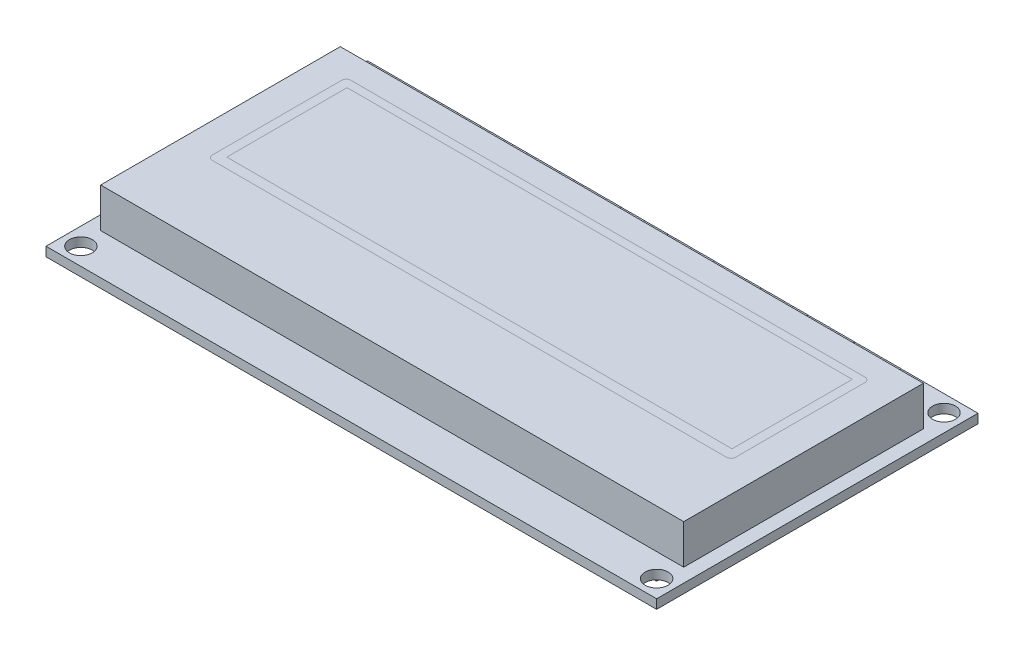
SolidWorks part; units mm, degrees
ref_plane "Front Plane" through (0, 0, 0) normal (0, 0, 1) x (1, 0, 0)
ref_plane "Top Plane" through (0, 0, 0) normal (0, 1, 0) x (1, 0, 0)
ref_plane "Right Plane" through (0, 0, 0) normal (1, 0, 0) x (0, 0, -1)
sketch "Sketch2" plane through (0, 0, 0) normal (0, 1, 0) x (1, 0, 0)
  line L1 (33.25, -17.5) -> (-33.25, -17.5)
  line L2 (33.25, -17.5) -> (33.25, 17.5)
  line L3 (33.25, 17.5) -> (-33.25, 17.5)
  line L4 (-33.25, -17.5) -> (-33.25, 17.5)
  line L5 (33.25, -17.5) -> (-33.25, 17.5) construction
  line L6 (33.25, 17.5) -> (-33.25, -17.5) construction
  point P0 (0, 0)
  dimension "D1" = 66.5
  dimension "D2" = 35
extrude "Boss-Extrude1" add sketch "Sketch2" along normal mid plane 1
hole_wizard "Ø2.5 (2.5) Diameter Hole1" positions "Sketch5" profile "Sketch3" hole size "Ø2.5" standard "ANSI Metric" end condition through all
sketch "Sketch5" plane through (0, 0.5, 0) normal (0, 1, 0) x (1, 0, 0)
  line L0 (-33.25, -17.5) -> (33.25, -17.5) construction
  line L1 (-33.25, 17.5) -> (-33.25, -17.5) construction
  point P0 (-31.35, -15.6)
  point P2 (-31.35, 15.7)
  point P4 (31.35, 15.7)
  point P6 (31.35, -15.6)
  dimension "D1" = 1.9
  dimension "D2" = 62.7
  dimension "D3" = 1.9
  dimension "D4" = 31.3
sketch "Sketch3" plane through (-31.35, 0.5, 15.6) normal (1, 0, 0) x (0, 0, 1)
  line L0 (0, 0) -> (0, 1)
  line L1 (0, 1) -> (1.25, 1)
  line L2 (1.25, 1) -> (1.25, 0)
  line L5 (1.25, 0) -> (0, 0)
  line L11 (0, -6.35) -> (0, 107.95) construction
  dimension "Thru Hole Dia." = 2.5
  dimension "Thru Hole Depth" = 1
hole_wizard "Ø0.8 (0.8) Diameter Hole1" positions "Sketch7" profile "Sketch6" hole size "Ø0.8" standard "ANSI Metric" end condition through all
sketch "Sketch7" plane through (0, 0.5, 0) normal (0, 1, 0) x (1, 0, 0)
  line L0 (-24.16, 14.9) -> (-21.62, 14.9) construction
  line L1 (-33.25, 17.5) -> (-33.25, -17.5) construction
  line L4 (33.25, 17.5) -> (-33.25, 17.5) construction
  point P0 (-24.16, 14.9)
  point P6 (-21.62, 14.9)
  point P7 (-19.08, 14.9)
  point P8 (-16.54, 14.9)
  point P9 (-14, 14.9)
  point P10 (-11.46, 14.9)
  point P11 (-8.92, 14.9)
  point P12 (-6.38, 14.9)
  point P13 (-3.84, 14.9)
  point P14 (-1.3, 14.9)
  point P15 (1.24, 14.9)
  point P16 (3.78, 14.9)
  point P17 (6.32, 14.9)
  point P18 (8.86, 14.9)
  point P19 (11.4, 14.9)
  point P20 (13.94, 14.9)
  point P21 (16.48, 14.9)
  point P22 (19.02, 14.9)
  point P23 (21.56, 14.9)
  point P24 (24.1, 14.9)
  dimension "D5" = 2.6
  dimension "D2" = 2.54
  dimension "D3" = 48.26
  dimension "D4" = 9.09
  dimension "D1" = 20
sketch "Sketch6" plane through (-24.16, 0.5, -14.9) normal (1, 0, 0) x (0, 0, 1)
  line L0 (0, 0) -> (0, 1)
  line L1 (0, 1) -> (0.4, 1)
  line L2 (0.4, 1) -> (0.4, 0)
  line L5 (0.4, 0) -> (0, 0)
  line L11 (0, -6.35) -> (0, 107.95) construction
  dimension "Thru Hole Dia." = 0.8
  dimension "Thru Hole Depth" = 1
sketch "Sketch8" plane through (0, 0.5, 0) normal (0, 1, 0) x (1, 0, 0)
  line L0 (-24.96, 14.9) -> (-24.96, 17.5)
  line L1 (33.25, 17.5) -> (-33.25, 17.5) construction
  line L2 (-24.96, 17.5) -> (-23.36, 17.5)
  line L3 (-23.36, 17.5) -> (-23.36, 14.9)
  arc A0 (-24.96, 14.9) -> (-23.36, 14.9) centre (-24.16, 14.9) ccw
  circle A2 centre (-24.16, 14.9) radius 0.4 construction
  circle A3 centre (-24.16, 14.9) radius 0.4
  dimension "D1" = 1.6
  dimension "D2" = 3.4
extrude "Boss-Extrude2" add sketch "Sketch8" along normal blind 0.01
pattern_linear "LPattern1" count 20 spacing 2.54 along (1, 0, 0) of "Boss-Extrude2"
mirror "Mirror3" about plane through (0, 0, 0) normal (0, 1, 0) of "Boss-Extrude2", "LPattern1"
sketch "Sketch10" plane through (0, 0.5, 0) normal (0, 1, 0) x (1, 0, 0)
  line L0 (-33.25, 17.5) -> (-33.25, -17.5) construction
  line L1 (31.75, -13.05) -> (-31.75, -13.05)
  line L2 (31.75, -13.05) -> (31.75, 13.05)
  line L3 (31.75, 13.05) -> (-31.75, 13.05)
  line L4 (-31.75, -13.05) -> (-31.75, 13.05)
  line L5 (31.75, -13.05) -> (-31.75, 13.05) construction
  line L6 (31.75, 13.05) -> (-31.75, -13.05) construction
  line L7 (-33.25, -17.5) -> (33.25, -17.5) construction
  point P0 (0, 0)
  dimension "D1" = 63.5
  dimension "D2" = 26.1
  dimension "D3" = 1.5
  dimension "D4" = 4.45
extrude "Boss-Extrude3" add sketch "Sketch10" along normal blind 4.3
sketch "Sketch11" plane through (0, 4.8, 0) normal (0, 1, 0) x (1, 0, 0)
  line L0 (-33.25, 17.5) -> (-33.25, -17.5) construction
  line L1 (28, -4.65) -> (-28, -4.65)
  line L2 (28.5, -4.15) -> (28.5, 9.95)
  line L3 (28, 10.45) -> (-28, 10.45)
  line L4 (-28.5, -4.15) -> (-28.5, 9.95)
  line L5 (28.5, -4.65) -> (-28.5, 10.45) construction
  line L6 (28.5, 10.45) -> (-28.5, -4.65) construction
  line L7 (-33.25, -17.5) -> (33.25, -17.5) construction
  arc A0 (-28, -4.65) -> (-28.5, -4.15) centre (-28, -4.15) cw
  arc A1 (28, -4.65) -> (28.5, -4.15) centre (28, -4.15) ccw
  arc A2 (28.5, 9.95) -> (28, 10.45) centre (28, 9.95) ccw
  arc A3 (-28, 10.45) -> (-28.5, 9.95) centre (-28, 9.95) ccw
  point P0 (0, 2.9)
  dimension "D5" = 0.5
  dimension "D1" = 15.1
  dimension "D2" = 57
  dimension "D3" = 4.75
  dimension "D4" = 12.85
split line "Split Line1"
sketch "Sketch12" plane through (0, 4.8, 0) normal (0, 1, 0) x (1, 0, 0)
  line L0 (-33.25, -17.5) -> (33.25, -17.5) construction
  line L1 (27.51, -3.55) -> (-27.51, -3.55)
  line L2 (27.51, -3.55) -> (27.51, 9.55)
  line L3 (27.51, 9.55) -> (-27.51, 9.55)
  line L4 (-27.51, -3.55) -> (-27.51, 9.55)
  line L5 (27.51, -3.55) -> (-27.51, 9.55) construction
  line L6 (27.51, 9.55) -> (-27.51, -3.55) construction
  line L7 (-33.25, 17.5) -> (-33.25, -17.5) construction
  point P0 (0, 3)
  dimension "D1" = 55.02
  dimension "D2" = 13.1
  dimension "D3" = 13.95
  dimension "D4" = 5.74
split line "Split Line2"
sketch "Sketch13" plane through (0, -0.5, 0) normal (0, -1, 0) x (1, 0, 0)
  line L1 (-28.1, 12.35) -> (28.1, 12.35)
  line L2 (-28.1, 12.35) -> (-28.1, -12.1)
  line L3 (-28.1, -12.1) -> (28.1, -12.1)
  line L4 (28.1, 12.35) -> (28.1, -12.1)
  line L5 (-28.1, 12.35) -> (28.1, -12.1) construction
  line L6 (-28.1, -12.1) -> (28.1, 12.35) construction
  arc A2 (24.9, -14.9) -> (23.3, -14.9) centre (24.1, -14.9) ccw construction
  circle A11 centre (31.35, 15.6) radius 1.25 construction
  circle A13 centre (-31.35, 15.6) radius 1.25 construction
  point P0 (0, 0.125)
  dimension "D1" = 2
  dimension "D2" = 2
  dimension "D3" = 2
  dimension "D4" = 2
extrude "Boss-Extrude4" add sketch "Sketch13" along normal blind 2.5
ref_plane "Horiz C/L" through (0, 0, -3) normal (0, 0, -1) x (-1, 0, 0)
ref_plane "Vert C/L" through (0, 0, 0) normal (1, 0, 0) x (0, 0, -1)
